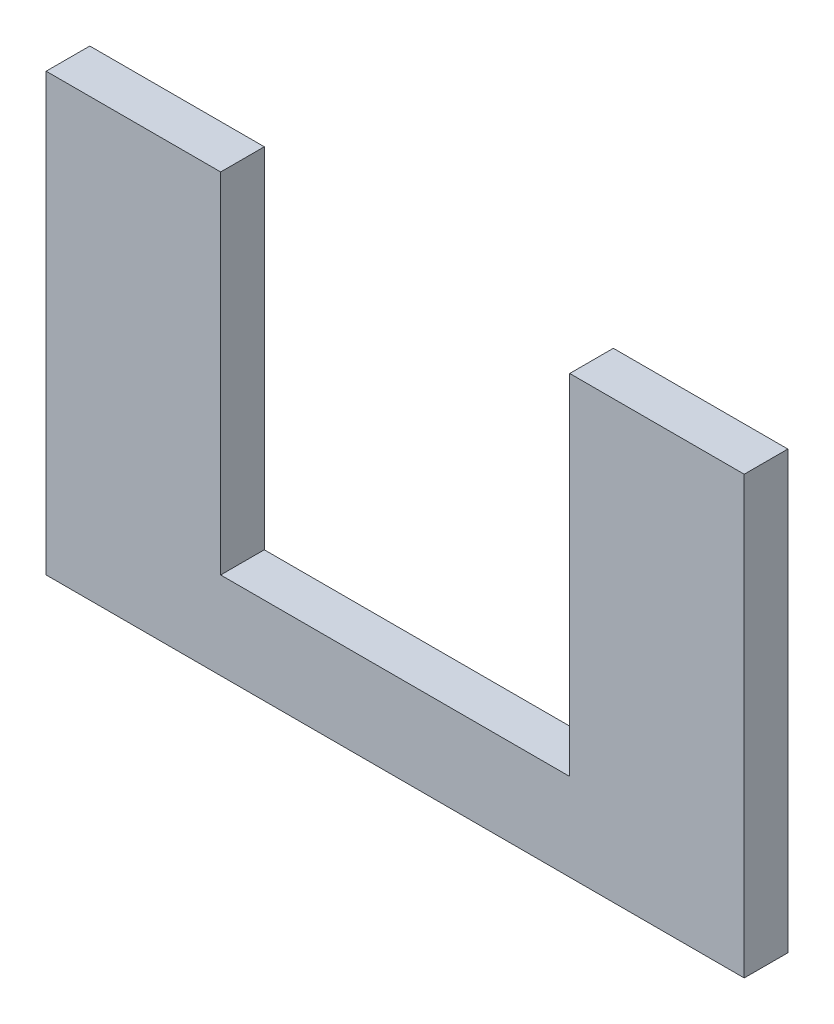
SolidWorks part; units mm, degrees
ref_plane "Front Plane" through (0, 0, 0) normal (0, 0, 1) x (1, 0, 0)
ref_plane "Top Plane" through (0, 0, 0) normal (0, 1, 0) x (1, 0, 0)
ref_plane "Right Plane" through (0, 0, 0) normal (1, 0, 0) x (0, 0, -1)
sketch "Sketch1" plane through (0, 0, 0) normal (0, 1, 0) x (1, 0, 0)
  line L0 (0, 0) -> (40, 0)
  line L1 (40, 0) -> (40, 2.5)
  line L2 (40, 2.5) -> (-40, 2.5)
  line L3 (-40, 2.5) -> (-40, -2.5)
  line L4 (-40, -2.5) -> (40, -2.5)
  line L5 (40, -2.5) -> (40, 0)
extrude "Boss-Extrude1" add sketch "Sketch1" along normal blind 50 contours L4 L5 L1 L2 L3 region at (39.1984, 0, 1.25)
sketch "Sketch2" plane through (0, 0, 2.5) normal (0, 0, 1) x (1, 0, 0)
  line L0 (0, 0) -> (0, 50)
  line L1 (-40, 50) -> (40, 50) construction
  line L2 (0, 50) -> (-20, 50)
  line L3 (-20, 50) -> (-20, 10)
  line L4 (-20, 10) -> (20, 10)
  line L5 (20, 10) -> (20, 50)
  line L6 (20, 50) -> (0, 50)
  line M4 (40, 50) -> (-40, 50)
extrude "Cut-Extrude1" cut sketch "Sketch2" against normal blind 50 contours L4 L5 L0 M4 | L3 L4 L0 M4 region at (-10, 30, 2.5) region at (10, 30, 2.5)
ref_plane "Plane1" through (0, 0, 0) normal (1, 0, 0) x (0, 0, -1)
ref_plane "Plane2" through (0, 0, 0) normal (0, -1, 0) x (-1, 0, 0)
ref_plane "Plane3" through (0, 0, 0) normal (0, 0, 1) x (1, 0, 0)
ref_axis "Axis1" through (0, 52.5, 0) along (0, -1, 0)
ref_axis "Axis2" through (0, 0, 2.75) along (0, 0, -1)
ref_point "Point1"
